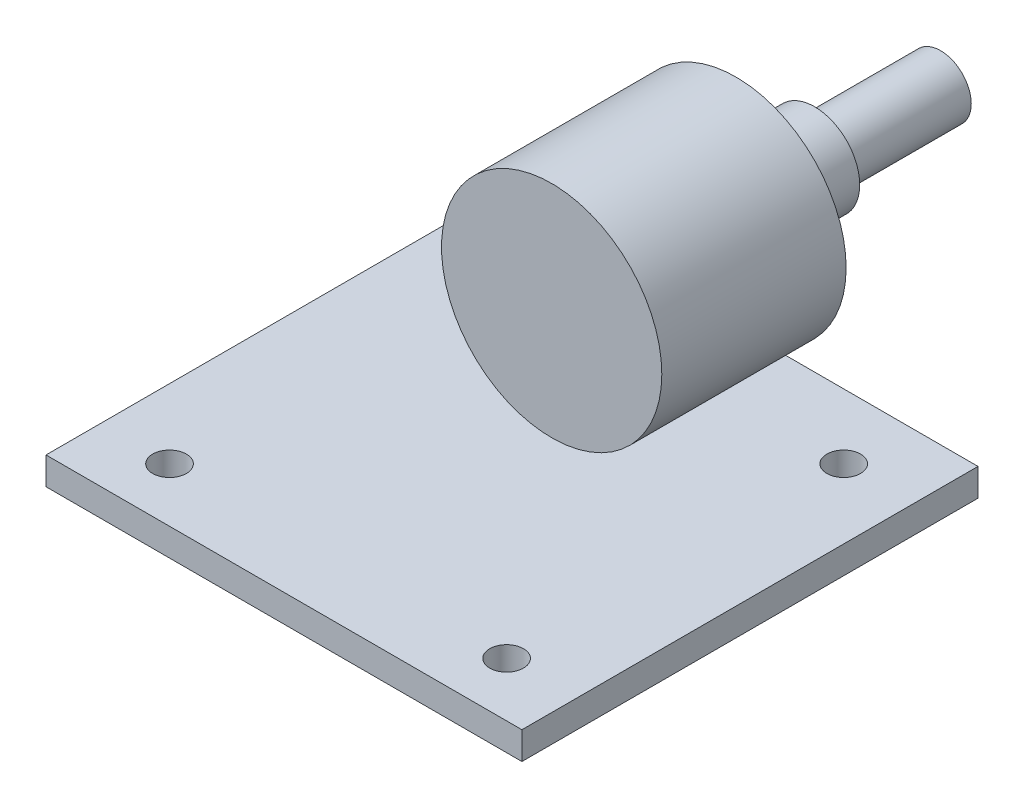
SolidWorks part; units mm, degrees
ref_plane "Alzado" through (0, 0, 0) normal (0, 0, 1) x (1, 0, 0)
ref_plane "Planta" through (0, 0, 0) normal (0, 1, 0) x (1, 0, 0)
ref_plane "Vista lateral" through (0, 0, 0) normal (1, 0, 0) x (0, 0, -1)
sketch "Croquis1" plane through (0, 0, 0) normal (1, 0, 0) x (0, 0, -1)
  line L0 (0, 0) -> (39.22, 0)
  line L1 (39.22, 0) -> (39.22, 3.1)
  line L2 (39.22, 3.1) -> (26.52, 3.1)
  line L3 (26.52, 3.1) -> (26.52, 4.55)
  line L4 (26.52, 4.55) -> (18.59, 4.55)
  line L5 (18.59, 4.55) -> (18.59, 11.11)
  line L6 (18.59, 11.11) -> (0, 11.11)
  line L7 (0, 11.11) -> (0, 0)
  dimension "D1" = 39.22
  dimension "D2" = 7.93
  dimension "D3" = 18.59
  dimension "D4" = 3.1
  dimension "D5" = 4.55
  dimension "D6" = 11.11
revolve "Revolución1" add sketch "Croquis1" angle 360 about L0
sketch "Croquis2" plane through (0, 0, 0) normal (0, 0, 1) x (1, 0, 0)
  line L0 (0, 11.11) -> (0, -13.89) construction
  line L2 (-24, -11.11) -> (24, -11.11)
  line L3 (-24, -11.11) -> (-24, -13.89)
  line L4 (-24, -13.89) -> (24, -13.89)
  line L5 (24, -11.11) -> (24, -13.89)
  circle A0 centre (0, 0) radius 11.11 construction
  dimension "D1" = 25
  dimension "D2" = 48
extrude "Saliente-Extruir1" add sketch "Croquis2" against normal blind 19 separate body
extrude "Saliente-Extruir2" add sketch "Croquis2<3>" along normal blind 27
sketch "Croquis2<3>" plane through (0, 0, 0) normal (0, 0, 1) x (1, 0, 0) same geometry as "Croquis2"
hole_wizard "Taladro de margen para M31" positions "Croquis4" profile "Croquis5" hole size "M3" standard "ISO" end condition through all
sketch "Croquis4" plane through (0, -11.11, 0) normal (0, 1, 0) x (1, 0, 0)
  line L0 (0, -1000) -> (0, 49000) construction
  line L2 (11.11, 18.59) -> (-11.11, 18.59) construction
  point P0 (-17, 12.458)
  point P6 (-17, -21.542)
  point P19 (17, -21.542)
  point P20 (17, 12.458)
  dimension "D1" = 34
  dimension "D2" = 34
  dimension "D3" = 6.132
sketch "Croquis5" plane through (-17, -11.11, -12.458) normal (1, 0, 0) x (0, 0, 1)
  line L0 (0, 0) -> (0, 2.78)
  line L1 (0, 2.78) -> (1.7, 2.78)
  line L2 (1.7, 2.78) -> (1.7, 0)
  line L5 (1.7, 0) -> (0, 0)
  line L11 (0, -6.35) -> (0, 107.95) construction
  dimension "Diámetro de taladro hasta el siguiente" = 3.4
  dimension "Profundidad de taladro hasta el siguiente" = 2.78
